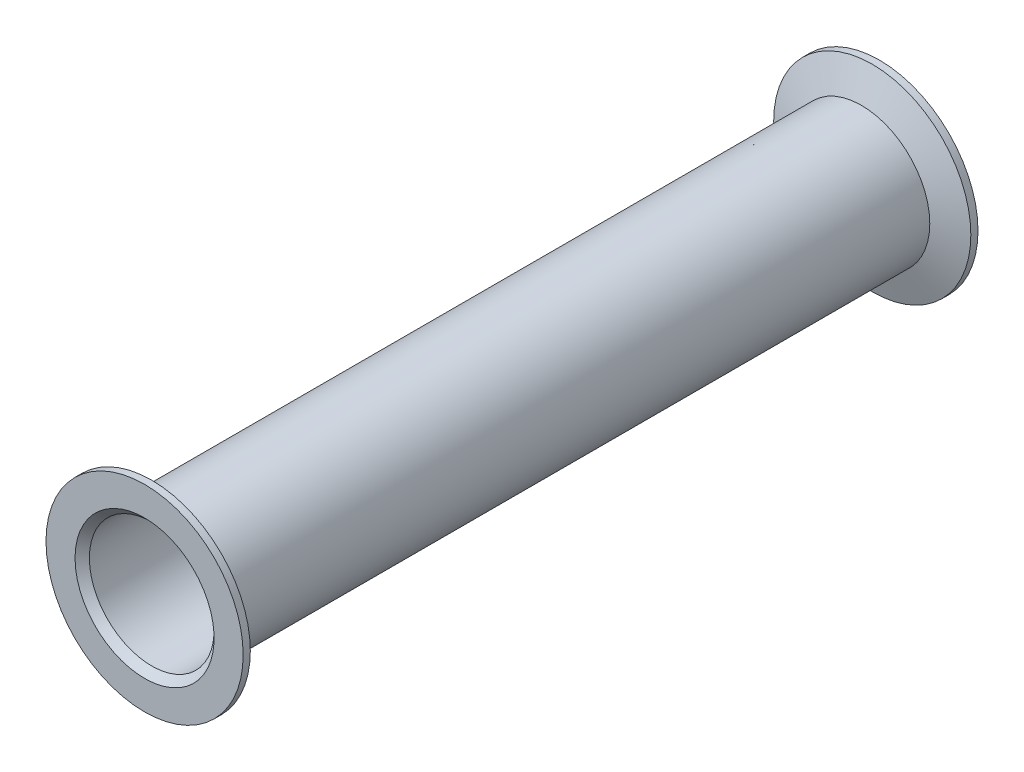
SolidWorks part; units mm, degrees
ref_plane "정면" through (0, 0, 0) normal (0, 0, 1) x (1, 0, 0)
ref_plane "윗면" through (0, 0, 0) normal (0, 1, 0) x (1, 0, 0)
ref_plane "우측면" through (0, 0, 0) normal (1, 0, 0) x (0, 0, -1)
sketch "스케치3" plane through (0, 0, 0) normal (0, 0, 1) x (1, 0, 0)
  circle A0 centre (0, 0) radius 19.05
  circle A1 centre (0, 0) radius 17.4
  dimension "D1" = 38.1
  dimension "D2" = 34.8
extrude "보스-돌출1" add sketch "스케치3" along normal mid plane 195
sketch "스케치4" plane through (0, 0, 0) normal (1, 0, 0) x (0, 0, -1)
  line L0 (102.5, 27.5) -> (100.5, 27.5)
  line L1 (-102.5, 27.5) -> (-102.5, 0)
  line L2 (-102.5, 0) -> (102.5, 0) construction
  line L3 (102.5, 0) -> (102.5, 27.5)
  line L4 (100.5, 27.5) -> (97.5, 19.05)
  line L5 (97.5, 19.05) -> (97.5, 0)
  line L6 (97.5, -19.05) -> (97.5, 19.05) construction
  line L7 (-97.5, 19.05) -> (-97.5, 0)
  line L8 (-97.5, 19.05) -> (-97.5, -19.05) construction
  line L9 (-102.5, 27.5) -> (-100.5, 27.5)
  line L10 (-100.5, 27.5) -> (-97.5, 19.05)
  dimension "D1" = 2
  dimension "D2" = 5
  dimension "D3" = 55
  dimension "D4" = 55
  dimension "D5" = 2
  dimension "D6" = 5
revolve "회전1" add sketch "스케치4" angle 360 about L2 region at (0, 12.6398, -100.1523) region at (0, 12.6398, 100.1523)
sketch "스케치5" plane through (0, 0, -102.5) normal (0, 0, -1) x (-1, 0, 0)
  circle A0 centre (0, 0) radius 17.4
  dimension "D1" = 34.8
extrude "컷-돌출1" cut sketch "스케치5" against normal through all
chamfer "모따기1" distance 2 angle 45 2 edges at (-17.4, 0, -102.5) (-17.4, 0, 102.5)
